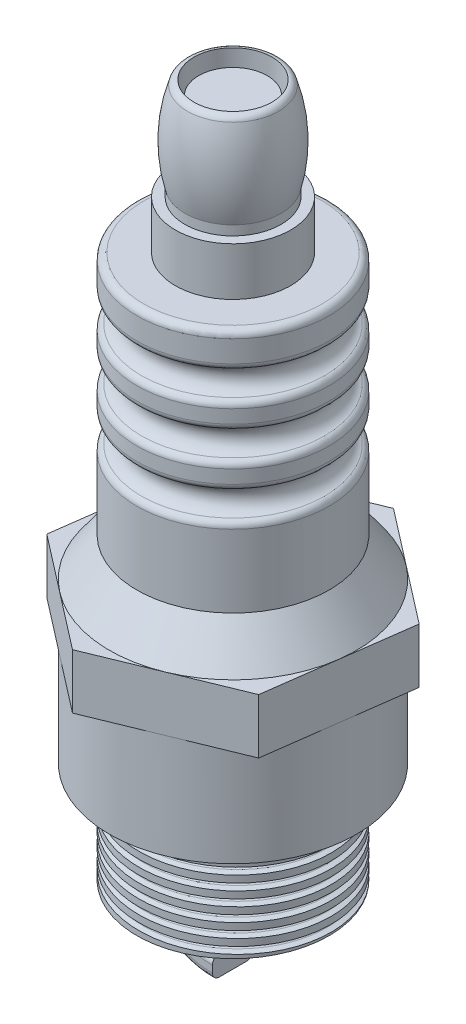
SolidWorks part; units mm, degrees
ref_plane "Front Plane" through (0, 0, 0) normal (0, 0, 1) x (1, 0, 0)
ref_plane "Top Plane" through (0, 0, 0) normal (0, 1, 0) x (1, 0, 0)
ref_plane "Right Plane" through (0, 0, 0) normal (1, 0, 0) x (0, 0, -1)
sketch "Sketch1" plane through (0, 0, 0) normal (0, 0, 1) x (1, 0, 0)
  line L23 (7, 0) -> (7, 7.4)
  line L24 (7, 7.4) -> (9, 7.4)
  line L30 (7, 0) -> (0, 0)
  line L32 (9, 7.4) -> (9, 19)
  line L33 (0, 0) -> (0, 50.5)
  line L34 (0, 50.5) -> (2.8427, 50.5)
  line L35 (9, 19) -> (7, 21.8)
  line L36 (7, 21.8) -> (0, 21.8)
  line L37 (7, 21.8) -> (7, 27.0858)
  line L38 (6.5, 39.6) -> (0, 39.6)
  line L39 (3.5, 43.8066) -> (3.5, 43.1125)
  line L40 (3.5, 43.1125) -> (4.2, 43.1125)
  line L41 (7, 21.8) -> (7, 27.0858)
  line L42 (7, 21.8) -> (7, 27.0858)
  line L43 (7, 37.5142) -> (7, 39.1)
  line L44 (7, 33.7142) -> (7, 34.6858)
  line L45 (7, 33.7142) -> (7, 34.6858)
  line L46 (7, 29.9142) -> (7, 30.8858)
  line L47 (7, 29.9142) -> (7, 30.8858)
  line L48 (7, 29.9142) -> (7, 30.8858)
  line L49 (4.2, 43.1125) -> (4.2, 39.6)
  arc A13 (3.3183, 50.1542) -> (3.5, 43.8066) centre (-7.4257, 46.6703) cw
  arc A14 (2.8427, 50.5) -> (3.3183, 50.1542) centre (2.8427, 50) cw
  arc A15 (7, 39.1) -> (6.5, 39.6) centre (6.5, 39.1) ccw
  arc A16 (6.6667, 37.0428) -> (6.6667, 35.1572) centre (7, 36.1) ccw
  arc A17 (6.6667, 33.2428) -> (6.6667, 31.3572) centre (7, 32.3) ccw
  arc A18 (6.6667, 29.4428) -> (6.6667, 27.5572) centre (7, 28.5) ccw
  arc A19 (7, 27.0858) -> (6.6667, 27.5572) centre (6.5, 27.0858) ccw
  arc A20 (7, 29.9142) -> (6.6667, 29.4428) centre (6.5, 29.9142) cw
  arc A21 (7, 30.8858) -> (6.6667, 31.3572) centre (6.5, 30.8858) ccw
  arc A22 (6.6667, 33.2428) -> (7, 33.7142) centre (6.5, 33.7142) ccw
  arc A23 (7, 34.6858) -> (6.6667, 35.1572) centre (6.5, 34.6858) ccw
  arc A24 (7, 37.5142) -> (6.6667, 37.0428) centre (6.5, 37.5142) cw
  point P70 (3.2, 50.5)
  point P73 (7, 39.6)
  point P100 (7, 37.1)
  dimension "D31" = 0.5
  dimension "D32" = 0.5
  dimension "D33" = 2
  dimension "D37" = 0.5
  dimension "D38" = 11.2947
  dimension "D24" = 7
  dimension "D25" = 11.6
  dimension "D26" = 7.4
  dimension "D27" = 50.5
  dimension "D28" = 3.2
  dimension "D29" = 2.8
  dimension "D30" = 17.8
  dimension "D34" = 3.5
  dimension "D35" = 3
  dimension "D36" = 3.8
  dimension "D39" = 0.6941
  dimension "D40" = 3.5125
  dimension "D41" = 0.7
  dimension "D42" = 7
  dimension "D43" = 4.2
  dimension "D44" = 9
revolve "Revolve1" add sketch "Sketch1" angle 360 about L33 region at (4.1499, 11.3404, 0) region at (3.3722, 30.6307, 0) region at (1.9312, 44.8679, 0)
ref_plane "Plane1" through (0, 19, 0) normal (0, 1, 0) x (1, 0, 0)
sketch "Sketch2" plane through (0, 19, 0) normal (0, 1, 0) x (1, 0, 0)
  line L1 (-8.2241, 6.3533) -> (-9.6142, -3.9456)
  line L2 (-9.6142, -3.9456) -> (-1.3901, -10.2989)
  line L3 (-1.3901, -10.2989) -> (8.2241, -6.3533)
  line L4 (8.2241, -6.3533) -> (9.6142, 3.9456)
  line L5 (9.6142, 3.9456) -> (1.3901, 10.2989)
  line L6 (1.3901, 10.2989) -> (-8.2241, 6.3533)
  circle A0 centre (0, 0) radius 9 construction
  circle A1 centre (0, 0) radius 9 construction
  dimension "D1" = 1.3901
extrude "Boss-Extrude1" add sketch "Sketch2" against normal blind 4
sketch "Sketch5" plane through (0, 7.4, 0) normal (0, -1, 0) x (1, 0, 0)
  circle A0 centre (0, 0) radius 7 construction
  circle A1 centre (0, 0) radius 7
curve "Helix/Spiral1" pitch 1 height 8.25 radius 7 left hand yes centre (0, 7.4, 0) axis (0, -1, 0) start towards (1, 0, 0)
sketch "Sketch6" plane through (0, 0, 0) normal (1, 0, 0) x (0, 0, -1)
  line L0 (6.6551, -0.7082) -> (7.0051, -0.6017)
  line L1 (7.0051, -0.6017) -> (7.0051, -1.1017)
  line L2 (7.0051, -1.1017) -> (6.6551, -0.9952)
  line L3 (7.0051, -0.8517) -> (6.1835, -0.8517) construction
  arc A0 (6.6551, -0.7082) -> (6.6551, -0.9952) centre (6.6988, -0.8517) ccw
  point P7 (6.5488, -0.8517)
  dimension "D1" = 0.15
  dimension "D2" = 0.5
  dimension "D3" = 0.35
sweep "Cut-Sweep1" cut profiles "Sketch6" path "Helix/Spiral1" align with end faces yes
sketch "Sketch7" plane through (0, 0, 0) normal (0, -1, 0) x (1, 0, 0)
  circle A0 centre (0, 0) radius 2.5
  circle A1 centre (0, 0) radius 3.75
  dimension "D1" = 7.5
  dimension "D2" = 5
extrude "Cut-Extrude1" cut sketch "Sketch7" against normal up to surface (7.4 mm away) up to face at (0.618, 7.4, -0.6332)
sketch "Sketch8" plane through (0, 0, 0) normal (0, -1, 0) x (1, 0, 0)
  circle A0 centre (0, 0) radius 1.25
  dimension "D1" = 2.5
extrude "Boss-Extrude2" add sketch "Sketch8" along normal blind 1
sketch "Sketch9" plane through (0, 0, 0) normal (0, -1, 0) x (1, 0, 0)
  line L0 (0, 0) -> (-15.7474, 0) construction
  line L2 (-5.25, 1.5) -> (-4.75, 1.5)
  line L3 (-5.75, 1) -> (-5.75, -1)
  line L4 (-5.25, -1.5) -> (-4.75, -1.5)
  line L5 (-4.25, 1) -> (-4.25, -1)
  line L6 (-5.75, 1.5) -> (-4.25, -1.5) construction
  line L7 (-5.75, -1.5) -> (-4.25, 1.5) construction
  arc A0 (-4.75, 1.5) -> (-4.25, 1) centre (-4.75, 1) cw
  arc A1 (-5.25, 1.5) -> (-5.75, 1) centre (-5.25, 1) ccw
  arc A2 (-5.75, -1) -> (-5.25, -1.5) centre (-5.25, -1) ccw
  arc A3 (-4.75, -1.5) -> (-4.25, -1) centre (-4.75, -1) ccw
  point P3 (-5, 0)
  dimension "D1" = 0.5
  dimension "D2" = 3
  dimension "D3" = 1.5
  dimension "D4" = 5
sketch "Sketch10" plane through (0, 0, 0) normal (0, 0, 1) x (1, 0, 0)
  line L0 (-5.75, 0) -> (-4.25, 0) construction
  arc A0 (-5, 0) -> (0, -4.855) centre (-0.0725, 0.0725) ccw
sweep "Sweep1" add profiles "Sketch9" path "Sketch10"
sketch "Sketch11" plane through (0, 50.5, 0) normal (0, 1, 0) x (1, 0, 0)
  circle A0 centre (0, 0) radius 2.8427 construction
  circle A1 centre (0, 0) radius 2.8427
extrude "Cut-Extrude2" cut sketch "Sketch11" against normal blind 2
sketch "Sketch12" plane through (0, 48.5, 0) normal (0, 1, 0) x (1, 0, 0)
  circle A0 centre (0, 0) radius 2.5
  dimension "D1" = 5
extrude "Boss-Extrude3" add sketch "Sketch12" along normal blind 1
